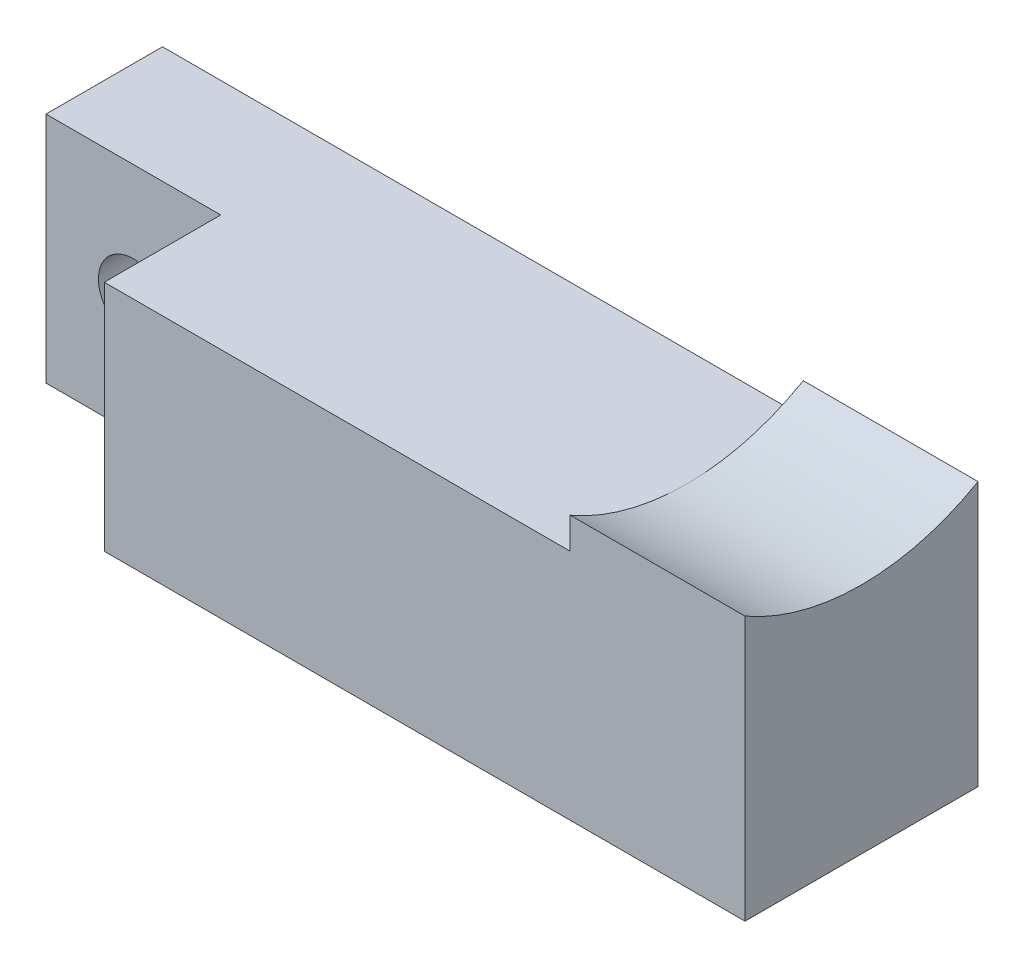
SolidWorks part; units mm, degrees
ref_plane "Alzado" through (0, 0, 0) normal (0, 0, 1) x (1, 0, 0)
ref_plane "Planta" through (0, 0, 0) normal (0, 1, 0) x (1, 0, 0)
ref_plane "Vista lateral" through (0, 0, 0) normal (1, 0, 0) x (0, 0, -1)
sketch "Croquis2" plane through (0, 0, 0) normal (0, 1, 0) x (1, 0, 0)
  line L1 (0, 0) -> (70, 0)
  line L2 (0, 0) -> (0, 20)
  line L3 (0, 20) -> (70, 20)
  line L4 (70, 0) -> (70, 20)
  dimension "D1" = 20
  dimension "D2" = 70
extrude "Saliente-Extruir1" add sketch "Croquis2" along normal blind 20 contours L2 L3 L4 L1
sketch "Croquis3" plane through (0, 0, 0) normal (0, 1, 0) x (1, 0, 0)
  line L1 (0, 0) -> (15, 0)
  line L2 (0, 0) -> (0, 10)
  line L3 (0, 10) -> (15, 10)
  line L4 (15, 0) -> (15, 10)
  dimension "D1" = 15
  dimension "D2" = 10
extrude "Cortar-Extruir3" cut sketch "Croquis3" against normal through all and the other way through all contours L2 L3 L4 L1
sketch "Croquis4" plane through (0, 0, 0) normal (0, 1, 0) x (1, 0, 0)
  line L0 (70, 0) -> (70, 20) construction
  line L1 (0, 20) -> (70, 20) construction
  circle A0 centre (24, 10) radius 2
  dimension "D1" = 4
  dimension "D2" = 46
  dimension "D3" = 10
extrude "Cortar-Extruir6" cut sketch "Croquis4" against normal blind 6 and the other way blind 6 contours A0
thread "Rosca1" pitch 0.7 method cut profile "Perfil de rosca2" start angle 0, offset 1, length 6, pitch 0.7, diameter 4
ref_plane "Plano4" through (22, 7, -10) normal (0, 0, 1) x (-1, 0, 0)
sketch "Perfil de rosca2" plane through (22, 7, -10) normal (0, 0, 1) x (-1, 0, 0)
  line L0 (0, 0) -> (0, 0.7) construction
  line L1 (0, 0) -> (0.3789, 0.2187)
  line L2 (0.3789, 0.2187) -> (0.3789, 0.3062)
  line L3 (0.3789, 0.3062) -> (0, 0.525)
  line L4 (0.3789, 0.2625) -> (0, 0.2625) construction
  line L11 (0, 0) -> (0, 0.525)
  point P2 (0, 0)
  dimension "Pitch" = 0.7
  dimension "Profile_Angle" = 60
  dimension "Profile_Land" = 0.0875
  dimension "Profile_Height" = 0.3789
sketch "Croquis12" plane through (0, 0, 0) normal (0, 0, 1) x (1, 0, 0)
  line L0 (0, 0) -> (15, 0) construction
  line L1 (0, 0) -> (0, 20) construction
  circle A0 centre (7.5, 10) radius 3
  dimension "D1" = 6
  dimension "D2" = 10
  dimension "D3" = 7.5
extrude "Cortar-Extruir7" cut sketch "Croquis12" against normal through all contours A0
sketch "Croquis13" plane through (0, 20, 0) normal (0, 1, 0) x (1, 0, 0)
  line L0 (0, 20) -> (70, 20) construction
  line L1 (70, 0) -> (55, 0)
  line L2 (70, 0) -> (70, 20)
  line L3 (70, 20) -> (55, 20)
  line L4 (55, 0) -> (55, 20)
  dimension "D1" = 15
extrude "Saliente-Extruir2" add sketch "Croquis13" along normal blind 2.6795
sketch "Croquis14" plane through (55, 0, 0) normal (-1, 0, 0) x (0, 0, 1)
  line L0 (-20, 22.6795) -> (0, 22.6795) construction
  arc A0 (-20, 22.6795) -> (0, 22.6795) centre (-10, 40) ccw
  dimension "D1" = 20
extrude "Cortar-Extruir8" cut sketch "Croquis14" against normal blind 15 and the other way through all contours A0
